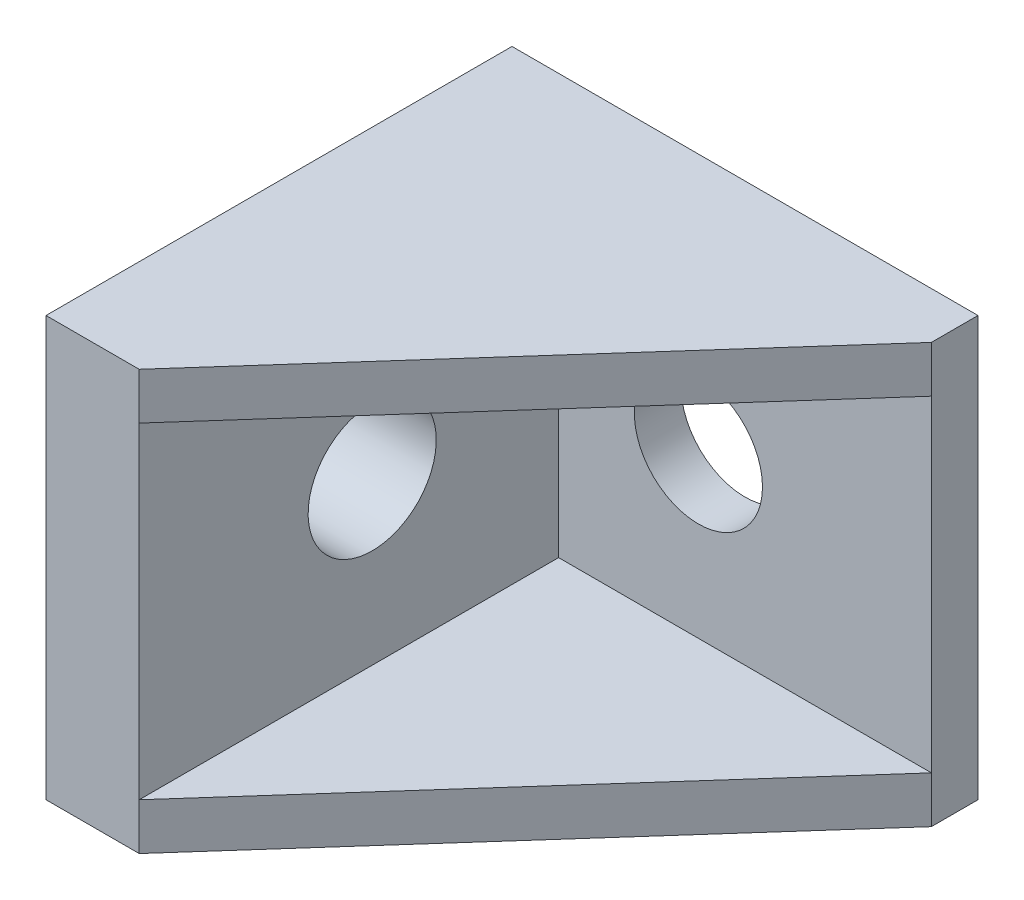
SolidWorks part; units mm, degrees
ref_plane "정면" through (0, 0, 0) normal (0, 0, 1) x (1, 0, 0)
ref_plane "윗면" through (0, 0, 0) normal (0, 1, 0) x (1, 0, 0)
ref_plane "우측면" through (0, 0, 0) normal (1, 0, 0) x (0, 0, -1)
sketch "스케치1" plane through (0, 0, 0) normal (0, 0, 1) x (1, 0, 0)
  line L1 (-10, 9) -> (10, 9)
  line L2 (-10, 9) -> (-10, -9)
  line L3 (-10, -9) -> (10, -9)
  line L4 (10, 9) -> (10, -9)
  line L5 (-10, 9) -> (10, -9) construction
  line L6 (-10, -9) -> (10, 9) construction
  point P0 (0, 0)
  dimension "D1" = 20
  dimension "D2" = 18
extrude "보스-돌출1" add sketch "스케치1" along normal blind 20
sketch "스케치2" plane through (0, 0, 20) normal (0, 0, 1) x (1, 0, 0)
  line L0 (10, -9) -> (10, 9) construction
  line L1 (10, 7) -> (-6, 7)
  line L2 (10, 7) -> (10, -7)
  line L3 (10, -7) -> (-6, -7)
  line L4 (-6, 7) -> (-6, -7)
  line L5 (-10, 9) -> (-10, -9) construction
  line L6 (10, 9) -> (-10, 9) construction
  line L7 (-10, -9) -> (10, -9) construction
  point P10 (0, 9)
  dimension "D1" = 4
  dimension "D2" = 2
  dimension "D3" = 2
extrude "컷-돌출1" cut sketch "스케치2" against normal blind 18
sketch "스케치4" plane through (0, -7, 0) normal (0, 1, 0) x (1, 0, 0)
  line L0 (-6, -20) -> (10, -2)
  line L1 (10, -2) -> (10, -20)
  line L2 (10, -20) -> (-6, -20)
extrude "컷-돌출2" cut sketch "스케치4" against normal through all both and the other way through all
sketch "스케치5" plane through (0, 0, 2) normal (0, 0, 1) x (1, 0, 0)
  line L0 (10, 7) -> (-6, 7) construction
  line L5 (-10, 9) -> (-10, -9) construction
  circle A2 centre (0, 0) radius 2.75
  dimension "D2" = 7
  dimension "D1" = 5.5
  dimension "D3" = 10
extrude "컷-돌출3" cut sketch "스케치5" against normal through all both
sketch "스케치6" plane through (-6, 0, 0) normal (1, 0, 0) x (0, 0, -1)
  line L0 (-2, 7) -> (-20, 7) construction
  line L5 (-20, 7) -> (-20, -7) construction
  circle A2 centre (-10, 0) radius 2.75
  dimension "D2" = 7
  dimension "D1" = 5.5
  dimension "D3" = 10
extrude "컷-돌출4" cut sketch "스케치6" against normal through all both
